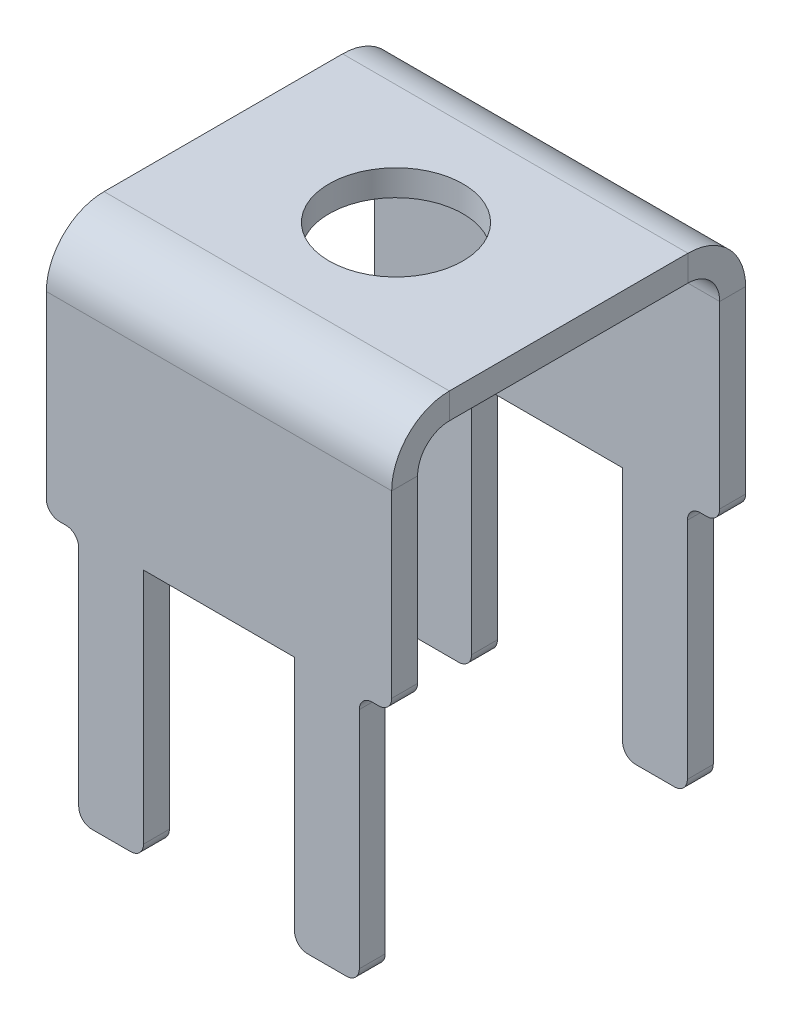
SolidWorks part; units mm, degrees
note: The reader was unsure of these and kept them because the rebuilt part matched: flange length of "边线-法兰1".
ref_plane "前视基准面" through (0, 0, 0) normal (0, 0, 1) x (1, 0, 0)
ref_plane "上视基准面" through (0, 0, 0) normal (0, 1, 0) x (1, 0, 0)
ref_plane "右视基准面" through (0, 0, 0) normal (1, 0, 0) x (0, 0, -1)
sketch "草图1" plane through (0, 0, 0) normal (0, 1, 0) x (1, 0, 0)
  line L0 (0, 11.0743) -> (0, -10.8834) construction
  line L1 (-4, 4.1) -> (4, 4.1)
  line L2 (-4, 4.1) -> (-4, -4.1)
  line L3 (-4, -4.1) -> (4, -4.1)
  line L4 (4, 4.1) -> (4, -4.1)
  line L5 (-14.2377, 0) -> (11.2071, 0) construction
  dimension "D1" = 8.2
  dimension "D2" = 8
sheet metal parameters "钣金1" thickness 0.6 parameters "D1"=0.7366
base flange "基体-法兰1" sketch "草图1" thickness 0.6 reverse thickness direction no parameters "D1"=0.7366
edge flange "边线-法兰1" sketch "草图8" flange profiles "草图8", "草图9" flange angle 90 flange length 11 flange position material inside bend radius 0.7366 thickness 0.6 relief rectangular parameters "D6"=10, "D8"=1
sketch "草图8" plane through (0, -0.6, 4.1) normal (0, 0, 1) x (-1, 0, 0)
  line L0 (4, 0) -> (-4, 0) construction
  line L1 (4, 0) -> (-4, 0)
  line L2 (-4, 0) -> (-4, 11)
  line L3 (-4, 11) -> (4, 11)
  line L4 (4, 11) -> (4, 0)
sketch "草图9" plane through (0, -0.6, -4.1) normal (0, 0, -1) x (1, 0, 0)
  line L0 (4, 0) -> (-4, 0) construction
  line L1 (4, 0) -> (-4, 0)
  line L2 (-4, 0) -> (-4, 11)
  line L3 (-4, 11) -> (4, 11)
  line L4 (4, 11) -> (4, 0)
bend "边线折弯1" bend radius 0.7366 bend angle 90 parameters "D5"=1
bend "边线折弯2" bend radius 0.7366 bend angle 90 parameters "D5"=2
sketch "草图10" plane through (0, -11.6, 0) normal (0, -1, 0) x (1, 0, 0)
  line L0 (0, 6.3976) -> (0, -6.8594) construction
  line L1 (-2.5, -6.8594) -> (-2.5, 6.3976) construction
  line L2 (-3.25, 4.3329) -> (-1.75, 4.3329)
  line L3 (-3.25, 4.3329) -> (-3.25, -5.1751)
  line L4 (-3.25, -5.1751) -> (-1.75, -5.1751)
  line L5 (-1.75, 4.3329) -> (-1.75, -5.1751)
  line L6 (2.5, -6.8594) -> (2.5, 6.3976) construction
  line L7 (1.75, 4.3329) -> (1.75, -5.1751)
  line L8 (3.25, -5.1751) -> (1.75, -5.1751)
  line L9 (3.25, 4.3329) -> (3.25, -5.1751)
  line L10 (3.25, 4.3329) -> (1.75, 4.3329)
  dimension "D1" = 1.5
  dimension "D2" = 5
extrude "切除-拉伸1" cut sketch "草图10" against normal blind 5.8 flip side to cut normal cut yes
fillet "圆角1" radius 0.3 8 edges at (-3.25, -11.6, -3.8) (-1.75, -11.6, -3.8) (1.75, -11.6, -3.8) (3.25, -11.6, -3.8) (3.25, -11.6, 3.8) (1.75, -11.6, 3.8) (-1.75, -11.6, 3.8) (-3.25, -11.6, 3.8)
fillet "圆角2" radius 0.3 8 edges at (-4, -5.8, 3.8) (-3.25, -5.8, 3.8) (-4, -5.8, -3.8) (-3.25, -5.8, -3.8) (4, -5.8, 3.8) (3.25, -5.8, 3.8) (4, -5.8, -3.8) (3.25, -5.8, -3.8)
sketch "草图11" plane through (0, 0, 0) normal (0, 1, 0) x (1, 0, 0)
  circle A0 centre (0, 0) radius 1.55
  dimension "D1" = 3.1
extrude "切除-拉伸2" cut sketch "草图11" against normal blind 5.8 normal cut yes
flat pattern "平板型式1" [suppressed]
sketch "折弯-线1" plane through (0, 0, 0) normal (0, 1, 0) x (1, 0, 0)
sketch3d "边界框1" [suppressed]
  line L0 (-4, -4, 0) -> (4, -4, 0) construction
  line L1 (-4, 4, 0) -> (4, 4, 0) construction
  line L2 (-4, -4, 0) -> (-4, 4, 0) construction
  line L3 (4, -4, 0) -> (4, 4, 0) construction
bend of the flat pattern "展开-<边线折弯1>1"
bend of the flat pattern "展开-<边线折弯2>1"
